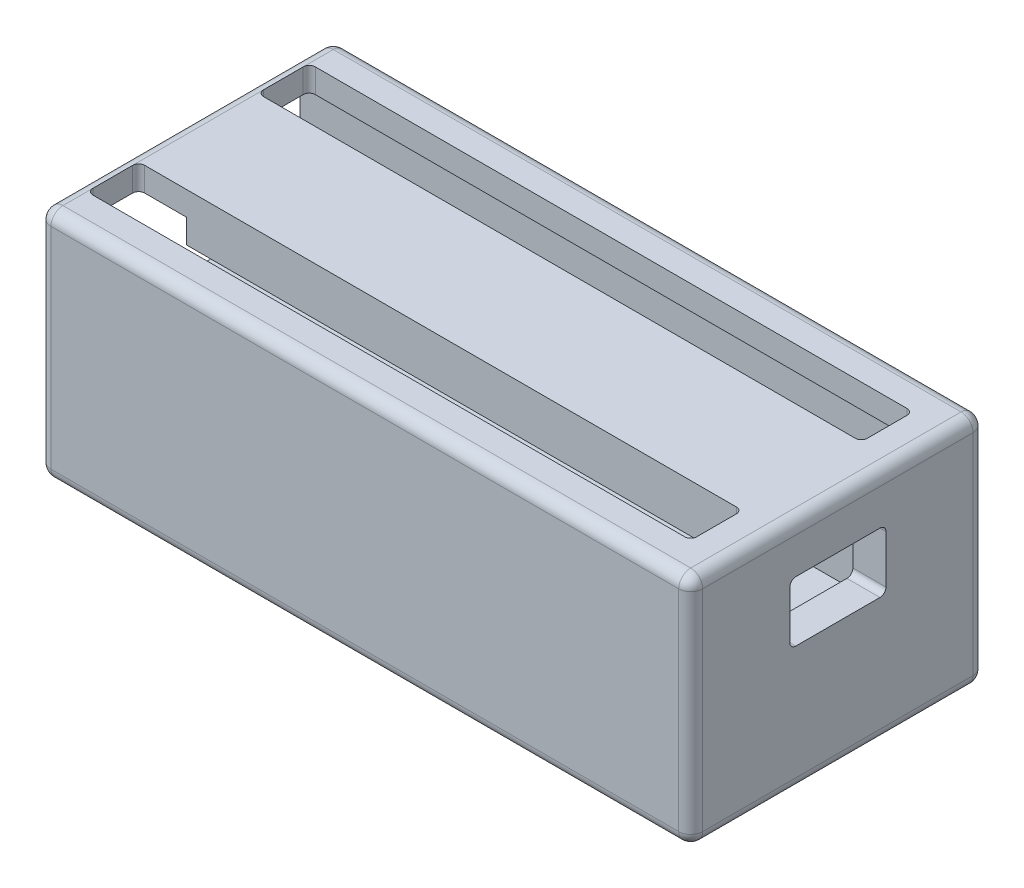
SolidWorks part; units mm, degrees
ref_plane "Alzado" through (0, 0, 0) normal (0, 0, 1) x (1, 0, 0)
ref_plane "Planta" through (0, 0, 0) normal (0, 1, 0) x (1, 0, 0)
ref_plane "Vista lateral" through (0, 0, 0) normal (1, 0, 0) x (0, 0, -1)
sketch "Sketch1" plane through (0, 0, 0) normal (0, 1, 0) x (1, 0, 0)
  line L1 (-25.125, -9.25) -> (25.125, -9.25)
  line L2 (-25.125, -9.25) -> (-25.125, 9.25)
  line L3 (-25.125, 9.25) -> (25.125, 9.25)
  line L4 (25.125, -9.25) -> (25.125, 9.25)
  line L5 (-25.125, -9.25) -> (25.125, 9.25) construction
  line L6 (-25.125, 9.25) -> (25.125, -9.25) construction
  point P0 (0, 0)
  dimension "D1" = 50.25
  dimension "D2" = 18.5
sketch "Sketch2" plane through (0, 0, 0) normal (0, 1, 0) x (1, 0, 0)
  line L4 (-26.125, 12.25) -> (-26.125, -12.25)
  line L5 (-25.125, -9.25) -> (-25.125, 9.25) construction
  line L8 (-28.125, 12.25) -> (-28.125, -12.25)
  line L9 (-28.125, -12.25) -> (28.125, -12.25)
  line L10 (28.125, -12.25) -> (28.125, 12.25)
  line L11 (28.125, 12.25) -> (-28.125, 12.25)
  line L12 (-28.125, 12.25) -> (-28.125, -12.25) construction
  line L13 (-26.125, -12.25) -> (28.125, -12.25)
  line L14 (28.125, -12.25) -> (28.125, 12.25)
  line L15 (28.125, 12.25) -> (-26.125, 12.25)
  dimension "D2" = 1
  dimension "D1" = 3
extrude "Boss-Extrude1" add sketch "Sketch2" along normal blind 2
sketch "Sketch3" plane through (0, 2, 0) normal (0, 1, 0) x (1, 0, 0)
  line L0 (-26.125, 12.25) -> (28.125, 12.25)
  line L1 (28.125, 12.25) -> (-26.125, 12.25) construction
  line L2 (28.125, 12.25) -> (28.125, -12.25)
  line L3 (28.125, -12.25) -> (-26.125, -12.25)
  line L4 (-26.125, -12.25) -> (-26.125, -9.5)
  line L6 (-26.125, -9.5) -> (25.375, -9.5)
  line L7 (25.375, -9.5) -> (25.375, 9.5)
  line L8 (25.375, 9.5) -> (-26.125, 9.5)
  line L9 (-26.125, 9.5) -> (-26.125, 12.25)
  line L10 (-25.125, 9.25) -> (25.125, 9.25) construction
  line L11 (25.125, -9.25) -> (25.125, 9.25) construction
  line L12 (-25.125, -9.25) -> (25.125, -9.25) construction
  line L13 (-26.125, 12.25) -> (-26.125, -12.25) construction
  point P11 (0, 0)
  point P21 (0, 0)
  point P22 (0, 0)
  point P25 (0, 0)
  dimension "D1" = 0.25
  dimension "D2" = 0.25
  dimension "D3" = 0.25
extrude "Boss-Extrude2" add sketch "Sketch3" along normal blind 15.5
sketch "Sketch5" plane through (0, 17.5, 0) normal (0, 1, 0) x (1, 0, 0)
  line L1 (-26.125, 12.25) -> (28.125, 12.25)
  line L2 (-26.125, 12.25) -> (-26.125, -12.25)
  line L3 (-26.125, -12.25) -> (28.125, -12.25)
  line L4 (28.125, 12.25) -> (28.125, -12.25)
  line L5 (-26.125, 12.25) -> (28.125, -12.25) construction
  line L6 (-26.125, -12.25) -> (28.125, 12.25) construction
  point P4 (1, 0)
extrude "Boss-Extrude3" add sketch "Sketch5" along normal blind 2
sketch "Sketch6" plane through (25.375, 0, 0) normal (-1, 0, 0) x (0, 0, 1)
  line L0 (-9.5, 2) -> (9.5, 2) construction
  line L1 (-5.75, 2) -> (5.75, 2)
  line L2 (-5.75, 2) -> (-5.75, 8.5)
  line L3 (-5.75, 8.5) -> (5.75, 8.5)
  line L4 (5.75, 2) -> (5.75, 8.5)
  line L5 (-5.75, 2) -> (5.75, 8.5) construction
  line L6 (-5.75, 8.5) -> (5.75, 2) construction
  line L7 (-9.5, 17.5) -> (9.5, 17.5) construction
  line L8 (-5.75, 17.5) -> (5.75, 17.5)
  line L9 (-5.75, 17.5) -> (-5.75, 15.5)
  line L10 (-5.75, 15.5) -> (5.75, 15.5)
  line L11 (5.75, 17.5) -> (5.75, 15.5)
  line L12 (-5.75, 17.5) -> (5.75, 15.5) construction
  line L13 (-5.75, 15.5) -> (5.75, 17.5) construction
  point P4 (0, 5.25)
  point P11 (0, 16.5)
  point P14 (0, 0)
  point P16 (0, 0)
  dimension "D1" = 6.5
  dimension "D2" = 11.5
  dimension "D3" = 2
extrude "Boss-Extrude4" add sketch "Sketch6" along normal up to vertex (51.5 mm away) up to point (-26.125, 2, 9.5)
sketch "Sketch8" plane through (0, 19.5, 0) normal (0, 1, 0) x (1, 0, 0)
  line L0 (25.125, -9.25) -> (25.125, 9.25) construction
  line L1 (-25.125, 9.25) -> (25.125, 9.25)
  line L2 (-25.125, 9.25) -> (-25.125, 4.95)
  line L3 (-25.125, 4.95) -> (25.125, 4.95)
  line L4 (25.125, 9.25) -> (25.125, 4.95)
  line L5 (-25.125, 9.25) -> (25.125, 4.95) construction
  line L6 (-25.125, 4.95) -> (25.125, 9.25) construction
  line L7 (-25.125, -9.25) -> (-25.125, 9.25) construction
  line L8 (25.125, -9.25) -> (-25.125, -9.25)
  line L9 (25.125, -9.25) -> (25.125, -4.95)
  line L10 (25.125, -4.95) -> (-25.125, -4.95)
  line L11 (-25.125, -9.25) -> (-25.125, -4.95)
  line L12 (25.125, -9.25) -> (-25.125, -4.95) construction
  line L13 (25.125, -4.95) -> (-25.125, -9.25) construction
  point P4 (0, 7.1)
  point P12 (0, -7.1)
  dimension "D1" = 4.3
  dimension "D2" = 4.3
extrude "Cut-Extrude1" cut sketch "Sketch8" against normal through all
sketch "Sketch9" plane through (-26.125, 0, 0) normal (-1, 0, 0) x (0, 0, 1)
  line L1 (-5.75, 15.5) -> (5.75, 15.5)
  line L2 (-5.75, 15.5) -> (-5.75, 17.5)
  line L3 (-5.75, 17.5) -> (5.75, 17.5)
  line L4 (5.75, 15.5) -> (5.75, 17.5)
  line L5 (-5.75, 15.5) -> (5.75, 17.5) construction
  line L6 (-5.75, 17.5) -> (5.75, 15.5) construction
  point P4 (0, 16.5)
extrude "Cut-Extrude2" cut sketch "Sketch9" against normal blind 5
sketch "Sketch10" plane through (25.375, 0, 0) normal (-1, 0, 0) x (0, 0, 1)
  line L0 (-5.75, 15.5) -> (5.75, 15.5) construction
  line L1 (-4, 15.5) -> (4, 15.5)
  line L2 (-4, 15.5) -> (-4, 10.5)
  line L3 (-4, 10.5) -> (4, 10.5)
  line L4 (4, 15.5) -> (4, 10.5)
  line L5 (-4, 15.5) -> (4, 10.5) construction
  line L6 (-4, 10.5) -> (4, 15.5) construction
  point P4 (0, 13)
  point P7 (0, 0)
  dimension "D1" = 8
  dimension "D2" = 5
extrude "Cut-Extrude3" cut sketch "Sketch10" against normal blind 5
fillet "Fillet1" radius 0.5 20 edges at (25.125, 18.5, -9.25) (25.125, 17.5, -4.95) (25.125, 17.5, 4.95) (25.125, 18.5, 9.25) (-25.125, 18.5, 9.25) (-25.125, 18.5, 4.95) (-25.125, 18.5, -9.25) (-25.125, 18.5, -4.95) (26.75, 15.5, -4) (26.75, 10.5, -4) (26.75, 10.5, 4) (26.75, 15.5, 4) (25.125, 1, -9.25) (25.125, 4.25, 4.95) (25.125, 1, 9.25) (25.125, 4.25, -4.95) (-25.125, 1, -9.25) (-25.125, 4.25, -4.95) (-25.125, 4.25, 4.95) (-25.125, 1, 9.25)
fillet "Fillet2" radius 1 12 edges at (28.125, 9.75, -12.25) (1, 19.5, -12.25) (-26.125, 9.75, -12.25) (1, 0, -12.25) (-26.125, 0, 0) (-26.125, 19.5, 0) (1, 19.5, 12.25) (-26.125, 9.75, 12.25) (1, 0, 12.25) (28.125, 9.75, 12.25) (28.125, 0, 0) (28.125, 19.5, 0)
